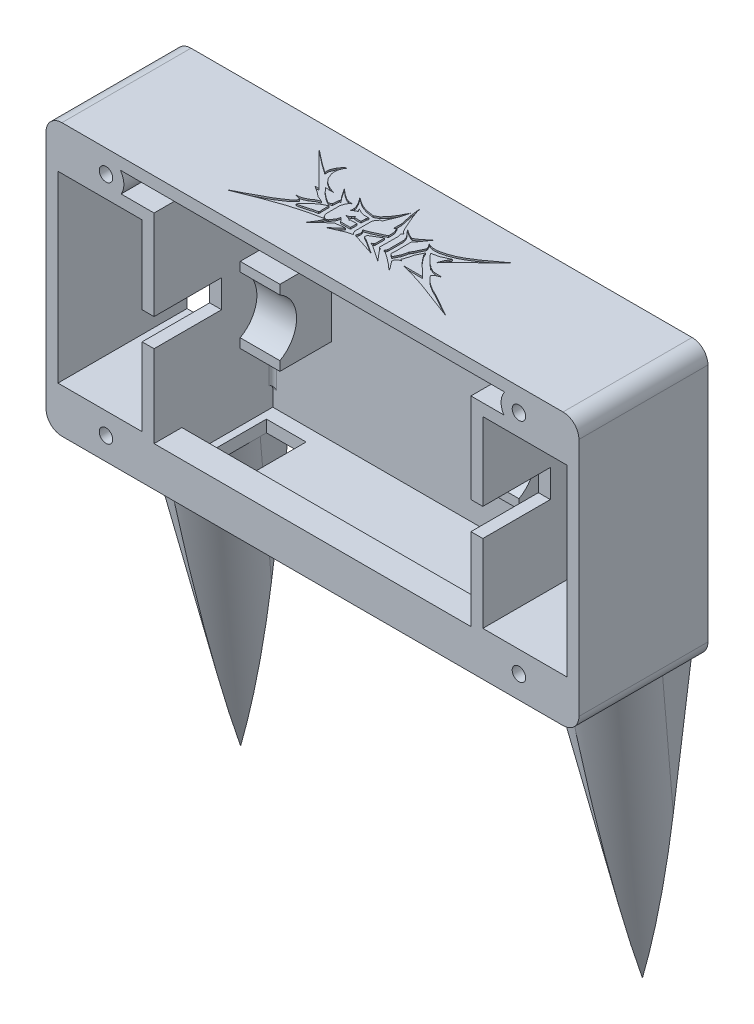
SolidWorks part; units mm, degrees
material "Overture Super PLA Plus"
ref_plane "Front Plane" through (0, 0, 0) normal (0, 0, 1) x (1, 0, 0)
ref_plane "Top Plane" through (0, 0, 0) normal (0, 1, 0) x (1, 0, 0)
ref_plane "Right Plane" through (0, 0, 0) normal (1, 0, 0) x (0, 0, -1)
sketch "Base_Footprint" plane through (0, 0, 0) normal (0, 0, 1) x (1, 0, 0)
  line L1 (-67.1, -34.2) -> (67.1, -34.2)
  line L2 (-67.1, -34.2) -> (-67.1, 34.2)
  line L3 (-67.1, 34.2) -> (67.1, 34.2)
  line L4 (67.1, -34.2) -> (67.1, 34.2)
  dimension "R1_Width" = 134.2
  dimension "R1_Length" = 68.4
  dimension "R1_X" = 67.1
  dimension "R1_Y" = 34.2
extrude "Unbroken_Floor" add sketch "Base_Footprint" along normal blind 2.6
sketch "Shell_Profile" plane through (0, 0, 0) normal (0, 0, 1) x (1, 0, 0)
  line L1 (-67.1, -34.2) -> (67.1, -34.2)
  line L2 (-67.1, -34.2) -> (-67.1, 34.2)
  line L3 (-67.1, 34.2) -> (67.1, 34.2)
  line L4 (67.1, -34.2) -> (67.1, 34.2)
  line L6 (-64.1, -31.2) -> (64.1, -31.2)
  line L7 (-64.1, -31.2) -> (-64.1, 31.2)
  line L8 (-64.1, 31.2) -> (64.1, 31.2)
  line L9 (64.1, -31.2) -> (64.1, 31.2)
  dimension "R1_Width" = 134.2
  dimension "R1_Length" = 68.4
  dimension "R1_X" = 67.1
  dimension "R1_Y" = 34.2
  dimension "R2_Width" = 128.2
  dimension "R2_Length" = 62.4
  dimension "R2_X" = 64.1
  dimension "R2_Y" = 31.2
extrude "Three_mm_Perimeter" add sketch "Shell_Profile" along normal blind 32.5
sketch "Wheel_Well_Profile" plane through (0, 0, 0) normal (0, 0, 1) x (1, 0, 0)
  line L1 (42.9, -23.1) -> (64.1, -23.1)
  line L2 (42.9, -23.1) -> (42.9, 23.1)
  line L3 (42.9, 23.1) -> (64.1, 23.1)
  line L4 (64.1, -23.1) -> (64.1, 23.1)
  line L6 (-64.1, -23.1) -> (-42.9, -23.1)
  line L7 (-64.1, -23.1) -> (-64.1, 23.1)
  line L8 (-64.1, 23.1) -> (-42.9, 23.1)
  line L9 (-42.9, -23.1) -> (-42.9, 23.1)
  dimension "R2_X" = 64.1
  dimension "R1_Width" = 21.2
  dimension "R1_Length" = 46.2
  dimension "R1_X" = 42.9
  dimension "R1_Y" = 23.1
  dimension "R2_Width" = 21.2
  dimension "R2_Length" = 46.2
  dimension "R2_Y" = 23.1
extrude "Open_Wheel_Wells" cut sketch "Wheel_Well_Profile" against normal blind 38 from offset 36
sketch "Wheel_Guard_Profile" plane through (0, 0, 0) normal (0, 0, 1) x (1, 0, 0)
  line L1 (39.9, -23.1) -> (42.9, -23.1)
  line L2 (39.9, -23.1) -> (39.9, 23.1)
  line L3 (39.9, 23.1) -> (42.9, 23.1)
  line L4 (42.9, -23.1) -> (42.9, 23.1)
  line L6 (-42.9, -23.1) -> (-39.9, -23.1)
  line L7 (-42.9, -23.1) -> (-42.9, 23.1)
  line L8 (-42.9, 23.1) -> (-39.9, 23.1)
  line L9 (-39.9, -23.1) -> (-39.9, 23.1)
  dimension "R1_Width" = 3
  dimension "R1_Length" = 46.2
  dimension "R1_X" = 39.9
  dimension "R1_Y" = 23.1
  dimension "R2_Width" = 3
  dimension "R2_Length" = 46.2
  dimension "R2_X" = 42.9
  dimension "R2_Y" = 23.1
extrude "Inner_Wheel_Guards" add sketch "Wheel_Guard_Profile" along normal blind 32.5
sketch "Wheel_Return_Profile" plane through (0, 0, 0) normal (0, 0, 1) x (1, 0, 0)
  line L1 (-64.1, -26.1) -> (-39.9, -26.1)
  line L2 (-64.1, -26.1) -> (-64.1, -23.1)
  line L3 (-64.1, -23.1) -> (-39.9, -23.1)
  line L4 (-39.9, -26.1) -> (-39.9, -23.1)
  line L6 (-64.1, 23.1) -> (-39.9, 23.1)
  line L7 (-64.1, 23.1) -> (-64.1, 26.1)
  line L8 (-64.1, 26.1) -> (-39.9, 26.1)
  line L9 (-39.9, 23.1) -> (-39.9, 26.1)
  line L11 (39.9, -26.1) -> (64.1, -26.1)
  line L12 (39.9, -26.1) -> (39.9, -23.1)
  line L13 (39.9, -23.1) -> (64.1, -23.1)
  line L14 (64.1, -26.1) -> (64.1, -23.1)
  line L16 (39.9, 23.1) -> (64.1, 23.1)
  line L17 (39.9, 23.1) -> (39.9, 26.1)
  line L18 (39.9, 26.1) -> (64.1, 26.1)
  line L19 (64.1, 23.1) -> (64.1, 26.1)
  dimension "R1_Width" = 24.2
  dimension "R1_Length" = 3
  dimension "R1_X" = 64.1
  dimension "R1_Y" = 26.1
  dimension "R2_Width" = 24.2
  dimension "R2_Length" = 3
  dimension "R2_X" = 64.1
  dimension "R2_Y" = 23.1
  dimension "R3_Width" = 24.2
  dimension "R3_Length" = 3
  dimension "R3_X" = 39.9
  dimension "R3_Y" = 26.1
  dimension "R4_Width" = 24.2
  dimension "R4_Length" = 3
  dimension "R4_X" = 39.9
  dimension "R4_Y" = 23.1
extrude "Wheel_Return_Ribs" add sketch "Wheel_Return_Profile" along normal blind 32.5
sketch "Shaft_Drop_In_Profile" plane through (0, 0, 0) normal (0, 0, 1) x (1, 0, 0)
  line L1 (-43.2, -3.5) -> (-39.5, -3.5)
  line L2 (-43.2, -3.5) -> (-43.2, 3.5)
  line L3 (-43.2, 3.5) -> (-39.5, 3.5)
  line L4 (-39.5, -3.5) -> (-39.5, 3.5)
  line L6 (39.5, -3.5) -> (43.2, -3.5)
  line L7 (39.5, -3.5) -> (39.5, 3.5)
  line L8 (39.5, 3.5) -> (43.2, 3.5)
  line L9 (43.2, -3.5) -> (43.2, 3.5)
  dimension "R1_Width" = 3.7
  dimension "R1_Length" = 7
  dimension "R1_X" = 43.2
  dimension "R1_Y" = 3.5
  dimension "R2_Width" = 3.7
  dimension "R2_Length" = 7
  dimension "R2_X" = 39.5
  dimension "R2_Y" = 3.5
extrude "Open_Shaft_Notches" cut sketch "Shaft_Drop_In_Profile" against normal blind 17 from offset 32.5
sketch "Lower_Cradle_Blocks_Profile" plane through (0, 0, 0) normal (0, 0, 1) x (1, 0, 0)
  line L1 (-35.1, -9.5) -> (-25.1, -9.5)
  line L2 (-35.1, -9.5) -> (-35.1, 9.5)
  line L3 (-35.1, 9.5) -> (-25.1, 9.5)
  line L4 (-25.1, -9.5) -> (-25.1, 9.5)
  line L6 (25.1, -9.5) -> (35.1, -9.5)
  line L7 (25.1, -9.5) -> (25.1, 9.5)
  line L8 (25.1, 9.5) -> (35.1, 9.5)
  line L9 (35.1, -9.5) -> (35.1, 9.5)
  dimension "R1_Width" = 10
  dimension "R1_Length" = 19
  dimension "R1_X" = 35.1
  dimension "R1_Y" = 9.5
  dimension "R2_Width" = 10
  dimension "R2_Length" = 19
  dimension "R2_X" = 25.1
  dimension "R2_Y" = 9.5
extrude "Lower_Motor_Cradles" add sketch "Lower_Cradle_Blocks_Profile" along normal blind 15.6
sketch "Lower_Cradle_Radius_Profile" plane through (0, 0, 0) normal (1, 0, 0) x (0, 0, -1)
  circle A0 centre (-19.6, 0) radius 8.2
  dimension "C1_Diameter" = 16.4
  dimension "Motor_Axis_Height" = 19.6
extrude "Lower_Cradle_Seats_R8p2" cut sketch "Lower_Cradle_Radius_Profile" against normal blind 72 from offset 36
sketch "Battery_Side_Guides_Profile" plane through (0, 0, 0) normal (0, 0, 1) x (1, 0, 0)
  line L1 (-31.5, 10) -> (-28.5, 10)
  line L2 (-31.5, 10) -> (-31.5, 31.2)
  line L3 (-31.5, 31.2) -> (-28.5, 31.2)
  line L4 (-28.5, 10) -> (-28.5, 31.2)
  line L6 (28.5, 10) -> (31.5, 10)
  line L7 (28.5, 10) -> (28.5, 31.2)
  line L8 (28.5, 31.2) -> (31.5, 31.2)
  line L9 (31.5, 10) -> (31.5, 31.2)
  dimension "R1_Width" = 3
  dimension "R1_Length" = 21.2
  dimension "R1_X" = 31.5
  dimension "R1_Y" = 10
  dimension "R2_Width" = 3
  dimension "R2_Length" = 21.2
  dimension "R2_X" = 28.5
  dimension "R2_Y" = 10
extrude "Battery_Side_Guides" add sketch "Battery_Side_Guides_Profile" along normal blind 5.6
sketch "Lid_Screw_Boss_Profile" plane through (0, 0, 0) normal (0, 0, 1) x (1, 0, 0)
  circle A0 centre (-52, -28.5) radius 4.5
  circle A1 centre (-52, 28.5) radius 4.5
  circle A2 centre (52, -28.5) radius 4.5
  circle A3 centre (52, 28.5) radius 4.5
  dimension "C1_Diameter" = 9
  dimension "C2_Diameter" = 9
  dimension "C3_Diameter" = 9
  dimension "C4_Diameter" = 9
extrude "Reinforced_M3_Bosses" add sketch "Lid_Screw_Boss_Profile" along normal blind 32.5
sketch "M3_Through_Holes_Profile" plane through (0, 0, 0) normal (0, 0, 1) x (1, 0, 0)
  circle A0 centre (-52, -28.5) radius 1.7
  circle A1 centre (-52, 28.5) radius 1.7
  circle A2 centre (52, -28.5) radius 1.7
  circle A3 centre (52, 28.5) radius 1.7
  dimension "C1_Diameter" = 3.4
  dimension "C2_Diameter" = 3.4
  dimension "C3_Diameter" = 3.4
  dimension "C4_Diameter" = 3.4
extrude "M3_Through_Holes" cut sketch "M3_Through_Holes_Profile" against normal blind 36 from offset 35.5
sketch "Captive_Nut_Pockets_Profile" plane through (0, 0, 0) normal (0, 0, 1) x (1, 0, 0)
  line L0 (-48.7091, -28.5) -> (-50.3546, -25.65)
  line L1 (-50.3546, -25.65) -> (-53.6454, -25.65)
  line L2 (-53.6454, -25.65) -> (-55.2909, -28.5)
  line L3 (-55.2909, -28.5) -> (-53.6454, -31.35)
  line L4 (-53.6454, -31.35) -> (-50.3546, -31.35)
  line L5 (-50.3546, -31.35) -> (-48.7091, -28.5)
  line L6 (-48.7091, 28.5) -> (-50.3546, 31.35)
  line L7 (-50.3546, 31.35) -> (-53.6454, 31.35)
  line L8 (-53.6454, 31.35) -> (-55.2909, 28.5)
  line L9 (-55.2909, 28.5) -> (-53.6454, 25.65)
  line L10 (-53.6454, 25.65) -> (-50.3546, 25.65)
  line L11 (-50.3546, 25.65) -> (-48.7091, 28.5)
  line L12 (55.2909, -28.5) -> (53.6454, -25.65)
  line L13 (53.6454, -25.65) -> (50.3546, -25.65)
  line L14 (50.3546, -25.65) -> (48.7091, -28.5)
  line L15 (48.7091, -28.5) -> (50.3546, -31.35)
  line L16 (50.3546, -31.35) -> (53.6454, -31.35)
  line L17 (53.6454, -31.35) -> (55.2909, -28.5)
  line L18 (55.2909, 28.5) -> (53.6454, 31.35)
  line L19 (53.6454, 31.35) -> (50.3546, 31.35)
  line L20 (50.3546, 31.35) -> (48.7091, 28.5)
  line L21 (48.7091, 28.5) -> (50.3546, 25.65)
  line L22 (50.3546, 25.65) -> (53.6454, 25.65)
  line L23 (53.6454, 25.65) -> (55.2909, 28.5)
extrude "M3_Hex_Nut_Pockets_Underside" cut sketch "Captive_Nut_Pockets_Profile" against normal blind 2.7 from offset 2.6
fillet "Outer_Corners_R4" radius 4 4 edges at (-67.1, 34.2, 16.25) (67.1, 34.2, 16.25) (67.1, -34.2, 16.25) (-67.1, -34.2, 16.25) tangent propagation no
fillet "Inner_Corners_R1" radius 1 4 edges at (-64.1, 31.2, 17.55) (64.1, 31.2, 17.55) (64.1, -31.2, 17.55) (-64.1, -31.2, 17.55) tangent propagation no
fillet "Wheel_Return_Root_Fillets_R1" radius 1 10 edges at (-44.0467, -26.1, 2.6) (-59.9533, -26.1, 2.6) (44.0467, 26.1, 2.6) (59.9533, 26.1, 2.6) (59.9533, -26.1, 2.6) (44.0467, -26.1, 2.6) (-59.9533, 26.1, 2.6) (-44.0467, 26.1, 2.6) (-39.9, 0, 2.6) (39.9, 0, 2.6) tangent propagation no
sketch "VIPER_Wordmark_Native_Profile" plane through (0, 0, 0) normal (0, 1, 0) x (1, 0, 0)
  line L0 (27.5, -26.3235) -> (17.4068, -22.5385)
  line L1 (17.4068, -22.5385) -> (13.8978, -21.4346)
  line L2 (13.8978, -21.4346) -> (11.3351, -20.7643)
  line L3 (11.3351, -20.7643) -> (11.2957, -20.6855)
  line L4 (11.2957, -20.6855) -> (15.948, -20.6855)
  line L5 (15.948, -20.6855) -> (14.2133, -18.9507)
  line L6 (14.2133, -18.9507) -> (13.543, -18.4776)
  line L7 (13.543, -18.4776) -> (12.3208, -17.1371)
  line L8 (12.3208, -17.1371) -> (11.3746, -15.8754)
  line L9 (11.3746, -15.8754) -> (11.0986, -15.1658)
  line L10 (11.0986, -15.1658) -> (10.0735, -17.2159)
  line L11 (10.0735, -17.2159) -> (10.0735, -17.6496)
  line L12 (10.0735, -17.6496) -> (9.5609, -19.2267)
  line L13 (9.5609, -19.2267) -> (9.3638, -19.5815)
  line L14 (9.3638, -19.5815) -> (9.7975, -19.8181)
  line L15 (9.7975, -19.8181) -> (9.7975, -19.897)
  line L16 (9.7975, -19.897) -> (9.5215, -19.9364)
  line L17 (9.5215, -19.9364) -> (9.0878, -20.2124)
  line L18 (9.0878, -20.2124) -> (8.7724, -20.5278)
  line L19 (8.7724, -20.5278) -> (8.6147, -20.8432)
  line L20 (8.6147, -20.8432) -> (8.6541, -21.2375)
  line L21 (8.6541, -21.2375) -> (9.7581, -22.6568)
  line L22 (9.7581, -22.6568) -> (10.31, -23.4453)
  line L23 (10.31, -23.4453) -> (10.2706, -23.5242)
  line L24 (10.2706, -23.5242) -> (9.1272, -22.4597)
  line L25 (9.1272, -22.4597) -> (7.1559, -20.922)
  line L26 (7.1559, -20.922) -> (5.9731, -20.1335)
  line L27 (5.9731, -20.1335) -> (5.224, -19.8575)
  line L28 (5.224, -19.8575) -> (5.4211, -19.621)
  line L29 (5.4211, -19.621) -> (5.6183, -19.069)
  line L30 (5.6183, -19.069) -> (5.6183, -15.2446)
  line L31 (5.6183, -15.2446) -> (5.5394, -14.8504)
  line L32 (5.5394, -14.8504) -> (5.224, -14.0224)
  line L33 (5.224, -14.0224) -> (3.6864, -12.2482)
  line L34 (3.6864, -12.2482) -> (5.0269, -13.155)
  line L35 (5.0269, -13.155) -> (5.9731, -13.6281)
  line L36 (5.9731, -13.6281) -> (6.2491, -13.6676)
  line L37 (6.2491, -13.6676) -> (7.4713, -12.879)
  line L38 (7.4713, -12.879) -> (9.3244, -11.3414)
  line L39 (9.3244, -11.3414) -> (7.6685, -13.707)
  line L40 (7.6685, -13.707) -> (6.9194, -14.5744)
  line L41 (6.9194, -14.5744) -> (6.9588, -18.1228)
  line L42 (6.9588, -18.1228) -> (6.8799, -19.5815)
  line L43 (6.8799, -19.5815) -> (7.629, -20.2518)
  line L44 (7.629, -20.2518) -> (8.457, -18.5959)
  line L45 (8.457, -18.5959) -> (8.8513, -17.0188)
  line L46 (8.8513, -17.0188) -> (9.2849, -16.3091)
  line L47 (9.2849, -16.3091) -> (10.3495, -14.0224)
  line L48 (10.3495, -14.0224) -> (10.1918, -13.5887)
  line L49 (10.1918, -13.5887) -> (9.6398, -12.7213)
  line L50 (9.6398, -12.7213) -> (10.2312, -12.9973)
  line L51 (10.2312, -12.9973) -> (10.9014, -13.155)
  line L52 (10.9014, -13.155) -> (12.1237, -13.155)
  line L53 (12.1237, -13.155) -> (13.9767, -12.7213)
  line L54 (13.9767, -12.7213) -> (15.7115, -12.0511)
  line L55 (15.7115, -12.0511) -> (17.3674, -11.1837)
  line L56 (17.3674, -11.1837) -> (19.5358, -9.8038)
  line L57 (19.5358, -9.8038) -> (24.267, -6.3342)
  line L58 (24.267, -6.3342) -> (20.0484, -10.474)
  line L59 (20.0484, -10.474) -> (17.4068, -12.9185)
  line L60 (17.4068, -12.9185) -> (15.5932, -14.7321)
  line L61 (15.5932, -14.7321) -> (14.6864, -15.836)
  line L62 (14.6864, -15.836) -> (14.647, -15.7177)
  line L63 (14.647, -15.7177) -> (15.0806, -14.6138)
  line L64 (15.0806, -14.6138) -> (15.8692, -13.155)
  line L65 (15.8692, -13.155) -> (13.6219, -14.1801)
  line L66 (13.6219, -14.1801) -> (11.7688, -14.5744)
  line L67 (11.7688, -14.5744) -> (13.5036, -16.4668)
  line L68 (13.5036, -16.4668) -> (14.4104, -17.2159)
  line L69 (14.4104, -17.2159) -> (14.7258, -17.3737)
  line L70 (14.7258, -17.3737) -> (15.0018, -17.7679)
  line L71 (15.0018, -17.7679) -> (15.1201, -17.6891)
  line L72 (15.1201, -17.6891) -> (15.9086, -18.1228)
  line L73 (15.9086, -18.1228) -> (16.5, -18.2805)
  line L74 (16.5, -18.2805) -> (18.4713, -18.3593)
  line L75 (18.4713, -18.3593) -> (17.2097, -18.8719)
  line L76 (17.2097, -18.8719) -> (16.8154, -19.1478)
  line L77 (16.8154, -19.1478) -> (16.6577, -19.3844)
  line L78 (16.6577, -19.3844) -> (17.1308, -20.0941)
  line L79 (17.1308, -20.0941) -> (18.5502, -21.3557)
  line L80 (18.5502, -21.3557) -> (20.0878, -22.302)
  line L81 (20.0878, -22.302) -> (21.31, -22.8934)
  line L82 (21.31, -22.8934) -> (27.5, -26.3235)
  line L83 (-27.4211, -26.2841) -> (-27.5, -26.2841)
  line L84 (-27.5, -26.2841) -> (-27.4606, -26.2052)
  line L85 (-27.4606, -26.2052) -> (-25.0161, -24.983)
  line L86 (-25.0161, -24.983) -> (-19.9695, -22.2231)
  line L87 (-19.9695, -22.2231) -> (-17.6039, -20.6461)
  line L88 (-17.6039, -20.6461) -> (-16.6971, -19.7787)
  line L89 (-16.6971, -19.7787) -> (-16.4211, -19.345)
  line L90 (-16.4211, -19.345) -> (-16.8943, -19.1084)
  line L91 (-16.8943, -19.1084) -> (-18.0771, -18.793)
  line L92 (-18.0771, -18.793) -> (-17.1308, -18.7536)
  line L93 (-17.1308, -18.7536) -> (-16.3029, -18.5565)
  line L94 (-16.3029, -18.5565) -> (-15.3961, -18.1228)
  line L95 (-15.3961, -18.1228) -> (-14.2527, -17.3342)
  line L96 (-14.2527, -17.3342) -> (-13.3065, -16.9794)
  line L97 (-13.3065, -16.9794) -> (-14.3315, -16.5063)
  line L98 (-14.3315, -16.5063) -> (-14.6075, -16.4668)
  line L99 (-14.6075, -16.4668) -> (-15.7903, -15.5206)
  line L100 (-15.7903, -15.5206) -> (-17.4068, -14.4955)
  line L101 (-17.4068, -14.4955) -> (-16.4211, -14.4955)
  line L102 (-16.4211, -14.4955) -> (-24.6219, -6.2554)
  line L103 (-24.6219, -6.2554) -> (-24.6219, -6.1765)
  line L104 (-24.6219, -6.1765) -> (-24.4642, -6.2554)
  line L105 (-24.4642, -6.2554) -> (-21.5466, -8.5421)
  line L106 (-21.5466, -8.5421) -> (-19.1416, -10.2375)
  line L107 (-19.1416, -10.2375) -> (-19.181, -9.4095)
  line L108 (-19.181, -9.4095) -> (-19.1022, -8.9758)
  line L109 (-19.1022, -8.9758) -> (-18.629, -7.8719)
  line L110 (-18.629, -7.8719) -> (-18.1165, -7.1622)
  line L111 (-18.1165, -7.1622) -> (-17.0914, -6.1765)
  line L112 (-17.0914, -6.1765) -> (-17.7616, -7.3593)
  line L113 (-17.7616, -7.3593) -> (-18.0376, -8.1873)
  line L114 (-18.0376, -8.1873) -> (-18.0771, -9.2518)
  line L115 (-18.0771, -9.2518) -> (-17.9588, -9.8038)
  line L116 (-17.9588, -9.8038) -> (-17.3674, -11.2231)
  line L117 (-17.3674, -11.2231) -> (-16.6183, -12.0511)
  line L118 (-16.6183, -12.0511) -> (-15.7115, -12.6819)
  line L119 (-15.7115, -12.6819) -> (-14.8441, -13.1156)
  line L120 (-14.8441, -13.1156) -> (-13.7007, -13.5099)
  line L121 (-13.7007, -13.5099) -> (-14.9229, -13.5493)
  line L122 (-14.9229, -13.5493) -> (-15.8297, -13.3916)
  line L123 (-15.8297, -13.3916) -> (-14.6864, -14.6138)
  line L124 (-14.6864, -14.6138) -> (-13.3065, -15.7177)
  line L125 (-13.3065, -15.7177) -> (-12.0842, -16.4668)
  line L126 (-12.0842, -16.4668) -> (-11.3351, -16.112)
  line L127 (-11.3351, -16.112) -> (-11.2563, -14.6138)
  line L128 (-11.2563, -14.6138) -> (-11.2168, -14.4561)
  line L129 (-11.2168, -14.4561) -> (-10.9409, -14.4167)
  line L130 (-10.9409, -14.4167) -> (-11.8082, -13.3127)
  line L131 (-11.8082, -13.3127) -> (-13.1093, -11.3808)
  line L132 (-13.1093, -11.3808) -> (-11.7688, -12.4848)
  line L133 (-11.7688, -12.4848) -> (-10.6649, -13.2339)
  line L134 (-10.6649, -13.2339) -> (-9.7975, -13.5887)
  line L135 (-9.7975, -13.5887) -> (-8.8513, -13.6281)
  line L136 (-8.8513, -13.6281) -> (-9.3638, -14.1013)
  line L137 (-9.3638, -14.1013) -> (-9.6398, -14.4955)
  line L138 (-9.6398, -14.4955) -> (-9.9946, -15.5206)
  line L139 (-9.9946, -15.5206) -> (-9.9946, -19.1478)
  line L140 (-9.9946, -19.1478) -> (-9.6398, -19.897)
  line L141 (-9.6398, -19.897) -> (-9.0484, -20.3306)
  line L142 (-9.0484, -20.3306) -> (-12.8728, -21.1586)
  line L143 (-12.8728, -21.1586) -> (-16.8548, -22.302)
  line L144 (-16.8548, -22.302) -> (-21.2312, -23.8396)
  line L145 (-21.2312, -23.8396) -> (-27.4211, -26.2841)
  line L146 (-10.586, -23.5636) -> (-10.6254, -23.4848)
  line L147 (-10.6254, -23.4848) -> (-9.4427, -21.6317)
  line L148 (-9.4427, -21.6317) -> (-8.8513, -20.2912)
  line L149 (-8.8513, -20.2912) -> (-8.5753, -20.2912)
  line L150 (-8.5753, -20.2912) -> (-8.3781, -20.1335)
  line L151 (-8.3781, -20.1335) -> (-7.5502, -18.9113)
  line L152 (-7.5502, -18.9113) -> (-7.2742, -18.0045)
  line L153 (-7.2742, -18.0045) -> (-6.3674, -19.0296)
  line L154 (-6.3674, -19.0296) -> (-3.9229, -19.0296)
  line L155 (-3.9229, -19.0296) -> (-3.9229, -17.3737)
  line L156 (-3.9229, -17.3737) -> (-5.5789, -17.4131)
  line L157 (-5.5789, -17.4131) -> (-5.6183, -17.7679)
  line L158 (-5.6183, -17.7679) -> (-5.776, -17.5314)
  line L159 (-5.776, -17.5314) -> (-6.1308, -17.2948)
  line L160 (-6.1308, -17.2948) -> (-7.1559, -16.9794)
  line L161 (-7.1559, -16.9794) -> (-6.6039, -16.8217)
  line L162 (-6.6039, -16.8217) -> (-6.1308, -16.5457)
  line L163 (-6.1308, -16.5457) -> (-5.6183, -15.9937)
  line L164 (-5.6183, -15.9937) -> (-5.5394, -16.388)
  line L165 (-5.5394, -16.388) -> (-3.9229, -16.3486)
  line L166 (-3.9229, -16.3486) -> (-3.8835, -15.0869)
  line L167 (-3.8835, -15.0869) -> (-3.6864, -14.6138)
  line L168 (-3.6864, -14.6138) -> (-4.6326, -14.6532)
  line L169 (-4.6326, -14.6532) -> (-5.5, -14.5349)
  line L170 (-5.5, -14.5349) -> (-6.8011, -13.9041)
  line L171 (-6.8011, -13.9041) -> (-6.6039, -14.3772)
  line L172 (-6.6039, -14.3772) -> (-6.3674, -14.4561)
  line L173 (-6.3674, -14.4561) -> (-6.3674, -14.5349)
  line L174 (-6.3674, -14.5349) -> (-6.9588, -14.8109)
  line L175 (-6.9588, -14.8109) -> (-7.7079, -15.4023)
  line L176 (-7.7079, -15.4023) -> (-7.5896, -14.9686)
  line L177 (-7.5896, -14.9686) -> (-7.5896, -14.2984)
  line L178 (-7.5896, -14.2984) -> (-7.7867, -13.6281)
  line L179 (-7.7867, -13.6281) -> (-8.3387, -12.5636)
  line L180 (-8.3387, -12.5636) -> (-9.2455, -11.302)
  line L181 (-9.2455, -11.302) -> (-7.7079, -12.4059)
  line L182 (-7.7079, -12.4059) -> (-6.6828, -12.9185)
  line L183 (-6.6828, -12.9185) -> (-5.4606, -13.3127)
  line L184 (-5.4606, -13.3127) -> (-3.6075, -13.5887)
  line L185 (-3.6075, -13.5887) -> (-2.543, -12.9973)
  line L186 (-2.543, -12.9973) -> (-1.5573, -11.9722)
  line L187 (-1.5573, -11.9722) -> (-0.414, -10.2375)
  line L188 (-0.414, -10.2375) -> (0.6505, -8.069)
  line L189 (0.6505, -8.069) -> (-0.0986, -10.7106)
  line L190 (-0.0986, -10.7106) -> (-1.3602, -13.707)
  line L191 (-1.3602, -13.707) -> (-1.5179, -13.5887)
  line L192 (-1.5179, -13.5887) -> (-1.7545, -13.707)
  line L193 (-1.7545, -13.707) -> (-2.1093, -14.1013)
  line L194 (-2.1093, -14.1013) -> (-2.5824, -14.8898)
  line L195 (-2.5824, -14.8898) -> (-2.5824, -19.2267)
  line L196 (-2.5824, -19.2267) -> (-2.3459, -19.7787)
  line L197 (-2.3459, -19.7787) -> (-1.9516, -20.1729)
  line L198 (-1.9516, -20.1729) -> (-3.4104, -20.5672)
  line L199 (-3.4104, -20.5672) -> (-7.1953, -22.2231)
  line L200 (-7.1953, -22.2231) -> (-5.9731, -21.2769)
  line L201 (-5.9731, -21.2769) -> (-4.3961, -19.8575)
  line L202 (-4.3961, -19.8575) -> (-4.3961, -19.7787)
  line L203 (-4.3961, -19.7787) -> (-5.1452, -19.8181)
  line L204 (-5.1452, -19.8181) -> (-6.8799, -20.0941)
  line L205 (-6.8799, -20.0941) -> (-8.733, -21.6711)
  line L206 (-8.733, -21.6711) -> (-10.586, -23.5636)
  line L207 (6.8405, -22.8934) -> (3.2527, -20.4884)
  line L208 (3.2527, -20.4884) -> (3.1344, -20.3306)
  line L209 (3.1344, -20.3306) -> (2.0699, -19.8575)
  line L210 (2.0699, -19.8575) -> (2.5036, -19.6604)
  line L211 (2.5036, -19.6604) -> (2.7007, -19.4238)
  line L212 (2.7007, -19.4238) -> (2.7007, -17.0188)
  line L213 (2.7007, -17.0188) -> (-0.0591, -18.6747)
  line L214 (-0.0591, -18.6747) -> (-0.0986, -19.3056)
  line L215 (-0.0986, -19.3056) -> (0.8871, -19.8181)
  line L216 (0.8871, -19.8181) -> (4.3566, -22.0654)
  line L217 (4.3566, -22.0654) -> (-1.3996, -20.1729)
  line L218 (-1.3996, -20.1729) -> (-1.6362, -20.0152)
  line L219 (-1.6362, -20.0152) -> (-1.3996, -19.345)
  line L220 (-1.3996, -19.345) -> (-1.3996, -18.793)
  line L221 (-1.3996, -18.793) -> (-1.5573, -18.3593)
  line L222 (-1.5573, -18.3593) -> (-1.7939, -18.0833)
  line L223 (-1.7939, -18.0833) -> (-1.7545, -18.0045)
  line L224 (-1.7545, -18.0045) -> (-0.2957, -17.4525)
  line L225 (-0.2957, -17.4525) -> (2.7007, -16.0332)
  line L226 (2.7007, -16.0332) -> (2.6613, -14.6532)
  line L227 (2.6613, -14.6532) -> (2.5036, -14.0618)
  line L228 (2.5036, -14.0618) -> (2.2276, -13.707)
  line L229 (2.2276, -13.707) -> (2.1882, -13.431)
  line L230 (2.1882, -13.431) -> (1.6756, -13.7464)
  line L231 (1.6756, -13.7464) -> (1.7545, -11.8539)
  line L232 (1.7545, -11.8539) -> (1.1237, -8.897)
  line L233 (1.1237, -8.897) -> (0.8082, -6.4131)
  line L234 (0.8082, -6.4131) -> (0.8871, -6.4525)
  line L235 (0.8871, -6.4525) -> (1.0448, -7.1622)
  line L236 (1.0448, -7.1622) -> (1.7151, -9.0152)
  line L237 (1.7151, -9.0152) -> (3.0556, -12.1299)
  line L238 (3.0556, -12.1299) -> (3.6864, -13.3127)
  line L239 (3.6864, -13.3127) -> (4.0806, -13.6281)
  line L240 (4.0806, -13.6281) -> (4.2778, -13.6676)
  line L241 (4.2778, -13.6676) -> (3.8835, -14.1013)
  line L242 (3.8835, -14.1013) -> (4.0806, -15.0081)
  line L243 (4.0806, -15.0081) -> (4.0412, -19.621)
  line L244 (4.0412, -19.621) -> (4.2384, -19.8181)
  line L245 (4.2384, -19.8181) -> (4.4749, -19.897)
  line L246 (4.4749, -19.897) -> (5.0269, -20.7249)
  line L247 (5.0269, -20.7249) -> (6.8405, -22.8934)
  line L248 (-15.9086, -20.6855) -> (-15.7903, -20.7249)
  line L249 (-15.7903, -20.7249) -> (-14.5681, -20.4489)
  line L250 (-14.5681, -20.4489) -> (-12.3996, -19.8181)
  line L251 (-12.3996, -19.8181) -> (-11.3746, -19.621)
  line L252 (-11.3746, -19.621) -> (-11.2563, -19.3056)
  line L253 (-11.2563, -19.3056) -> (-11.3351, -18.9113)
  line L254 (-11.3351, -18.9113) -> (-11.3351, -17.0188)
  line L255 (-11.3351, -17.0188) -> (-12.6362, -17.6496)
  line L256 (-12.6362, -17.6496) -> (-13.819, -18.517)
  line L257 (-13.819, -18.517) -> (-15.9086, -20.6855)
extrude "VIPER_Rear_Engraved" cut sketch "VIPER_Wordmark_Native_Profile" against normal blind 0.4 from offset 34.2
sketch "Sketch1" plane through (0, 0, 0) normal (0, 0, 1) x (1, 0, 0)
  line L0 (0, 0) -> (0, -36.802) construction
  line L1 (-48.4, -31.2) -> (-39.9, -31.2)
  line L2 (-48.4, -31.2) -> (-48.4, -26.1)
  line L3 (-48.4, -26.1) -> (-39.9, -26.1)
  line L4 (-39.9, -31.2) -> (-39.9, -26.1)
  line L5 (48.4, -31.2) -> (48.4, -26.1)
  line L6 (48.4, -26.1) -> (39.9, -26.1)
  line L7 (39.9, -31.2) -> (39.9, -26.1)
  line L8 (48.4, -31.2) -> (39.9, -31.2)
extrude "Boss-Extrude1" add sketch "Sketch1" along normal blind 32.5
sketch "Sketch2" plane through (-39.9, 0, 0) normal (1, 0, 0) x (0, 0, -1)
  line L1 (-32.5, -31.2) -> (-25.5, -31.2)
  line L2 (-32.5, -31.2) -> (-32.5, -24.2)
  line L3 (-32.5, -24.2) -> (-25.5, -24.2)
  line L4 (-25.5, -31.2) -> (-25.5, -24.2)
  dimension "D1" = 7
  dimension "D2" = 7
extrude "Boss-Extrude2" add sketch "Sketch2" along normal blind 82.5 and the other way blind 2
sketch "Sketch3" plane through (0, 0, 0) normal (0, 0, 1) x (1, 0, 0)
  line L1 (-55.6, 31.2) -> (-64.1, 31.2)
  line L2 (-55.6, 31.2) -> (-55.6, 26.1)
  line L3 (-55.6, 26.1) -> (-64.1, 26.1)
  line L4 (-64.1, 31.2) -> (-64.1, 26.1)
  line L5 (-55.6, -31.2) -> (-64.1, -31.2)
  line L6 (-55.6, -31.2) -> (-55.6, -26.1)
  line L7 (-55.6, -26.1) -> (-64.1, -26.1)
  line L8 (-64.1, -31.2) -> (-64.1, -26.1)
  line L9 (55.6, -31.2) -> (64.1, -31.2)
  line L10 (55.6, -31.2) -> (55.6, -26.1)
  line L11 (55.6, -26.1) -> (64.1, -26.1)
  line L12 (64.1, -31.2) -> (64.1, -26.1)
  line L13 (55.6, 31.2) -> (64.1, 31.2)
  line L14 (55.6, 31.2) -> (55.6, 26.1)
  line L15 (55.6, 26.1) -> (64.1, 26.1)
  line L16 (64.1, 31.2) -> (64.1, 26.1)
extrude "Boss-Extrude5" add sketch "Sketch3" along normal blind 32.5
sketch "Forks" plane through (0, -34.2, 0) normal (0, -1, 0) x (1, 0, 0)
  line L0 (0, 0) -> (0, 32.5) construction
  line L1 (-63.1, 32.5) -> (63.1, 32.5) construction
  line L2 (-63.1, 0) -> (63.1, 0) construction
  line L3 (-63.1, 32.5) -> (-38.1, 32.5)
  line L4 (-63.1, 32.5) -> (-63.1, 0)
  line L5 (-63.1, 0) -> (-38.1, 0)
  line L6 (-38.1, 32.5) -> (-38.1, 0)
  line L7 (63.1, 0) -> (38.1, 0)
  line L8 (38.1, 32.5) -> (38.1, 0)
  line L9 (63.1, 32.5) -> (38.1, 32.5)
  line L10 (63.1, 32.5) -> (63.1, 0)
  dimension "D1" = 25
sketch "Sketch4" plane through (0, -34.2, 0) normal (0, -1, 0) x (1, 0, 0)
  line L0 (-38.1, 32.5) -> (-38.1, 0) construction
  line L1 (-38.1, 24) -> (-28.1, 24)
  line L2 (-38.1, 24) -> (-38.1, 6)
  line L3 (-38.1, 6) -> (-28.1, 6)
  line L4 (-28.1, 24) -> (-28.1, 6)
  line L5 (-63.1, 0) -> (63.1, 0) construction
  dimension "D1" = 18
  dimension "D2" = 6
  dimension "D3" = 10
extrude "Cut-Extrude1" cut sketch "Sketch4" against normal blind 10
sketch "Sketch6" plane through (0, 0, 0) normal (0, 0, 1) x (1, 0, 0)
  line L0 (-50.6, -34.2) -> (-50.6, -134.2) construction
  line L1 (-63.1, -34.2) -> (-38.1, -34.2) construction
  line L2 (-38.1, -34.2) -> (-63.1, -34.2)
  line L3 (-63.1, -34.2) -> (-50.6, -134.2)
  line L4 (-38.1, -34.2) -> (-50.6, -134.2)
  line L5 (0, -34.2) -> (0, -134.2) construction
  line L6 (-63.1, -34.2) -> (63.1, -34.2) construction
  line L7 (38.1, -34.2) -> (63.1, -34.2)
  line L8 (38.1, -34.2) -> (50.6, -134.2)
  line L9 (63.1, -34.2) -> (50.6, -134.2)
  dimension "D1" = 100
  dimension "D2" = 12.5
extrude "Boss-Extrude7" add sketch "Sketch6" along normal blind 20
sketch "Sketch8" plane through (0, 0, 0) normal (1, 0, 0) x (0, 0, -1)
  line L0 (-20, -34.2) -> (0, -134.2)
  line L1 (0, -134.2) -> (-20, -134.2)
  line L2 (-20, -134.2) -> (-20, -34.2)
extrude "Cut-Extrude3" cut sketch "Sketch8" against normal blind 78 and the other way blind 70
fillet "Fillet3" radius 12.5 4 edges at (-44.35, -84.2, 10) (-56.85, -84.2, 10) (44.35, -84.2, 10) (56.85, -84.2, 10)
equation "\"Overall_Width\"= 134.2mm"
equation "\"Overall_Length\"= 68.4mm"
equation "\"Wall\"= 3mm"
equation "\"Floor\"= 2.6mm"
equation "\"Case_Height\"= 32.5mm"
equation "\"Lid_Thickness\"= 3mm"
equation "\"Wheel_Diameter\"= 43.2mm"
equation "\"Wheel_Width\"= 14mm"
equation "\"Wheel_Bay_Inner_X\"= 42.9mm"
equation "\"Wheel_Radial_Clearance\"= 1.5mm"
equation "\"Wheel_Bay_Half_Length\"= \"Wheel_Diameter\"/2+\"Wheel_Radial_Clearance\""
equation "\"Ground_Clearance\"= 2mm"
equation "\"Motor_Axis_Z\"= \"Wheel_Diameter\"/2-\"Ground_Clearance\""
equation "\"Motor_Face_X\"= 38.1mm"
equation "\"Motor_Clamp_Radius\"= 8.2mm"
equation "\"Screw_Clearance\"= 3.4mm"
equation "\"Nut_AF_Clearance\"= 5.7mm"
equation "\"Engraving_Depth\"= 0.4mm"
equation "\"Hub_Offset_Min_Allowed\"= \"Wheel_Bay_Inner_X\"+1mm-\"Motor_Face_X\""
equation "\"Hub_Offset_Max_Allowed\"= \"Overall_Width\"/2-\"Wall\"-1mm-\"Wheel_Width\"-\"Motor_Face_X\""
equation "\"R1_Width@Base_Footprint\" = \"Overall_Width\""
equation "\"R1_Length@Base_Footprint\" = \"Overall_Length\""
equation "\"R1_X@Base_Footprint\" = \"Overall_Width\"/2"
equation "\"R1_Y@Base_Footprint\" = \"Overall_Length\"/2"
equation "\"D1@Unbroken_Floor\" = \"Floor\""
equation "\"R1_Width@Shell_Profile\" = \"Overall_Width\""
equation "\"R1_Length@Shell_Profile\" = \"Overall_Length\""
equation "\"R1_X@Shell_Profile\" = \"Overall_Width\"/2"
equation "\"R1_Y@Shell_Profile\" = \"Overall_Length\"/2"
equation "\"R2_Width@Shell_Profile\" = \"Overall_Width\"-2*\"Wall\""
equation "\"R2_Length@Shell_Profile\" = \"Overall_Length\"-2*\"Wall\""
equation "\"R2_X@Shell_Profile\" = \"Overall_Width\"/2-\"Wall\""
equation "\"R2_Y@Shell_Profile\" = \"Overall_Length\"/2-\"Wall\""
equation "\"D1@Three_mm_Perimeter\" = \"Case_Height\""
equation "\"R1_Width@Wheel_Well_Profile\" = \"Overall_Width\"/2-\"Wall\"-\"Wheel_Bay_Inner_X\""
equation "\"R1_Length@Wheel_Well_Profile\" = 2*\"Wheel_Bay_Half_Length\""
equation "\"R1_X@Wheel_Well_Profile\" = \"Wheel_Bay_Inner_X\""
equation "\"R1_Y@Wheel_Well_Profile\" = \"Wheel_Bay_Half_Length\""
equation "\"R2_Width@Wheel_Well_Profile\" = \"Overall_Width\"/2-\"Wall\"-\"Wheel_Bay_Inner_X\""
equation "\"R2_Length@Wheel_Well_Profile\" = 2*\"Wheel_Bay_Half_Length\""
equation "\"R2_X@Wheel_Well_Profile\" = \"Overall_Width\"/2-\"Wall\""
equation "\"R2_Y@Wheel_Well_Profile\" = \"Wheel_Bay_Half_Length\""
equation "\"D1@Inner_Wheel_Guards\" = \"Case_Height\""
equation "\"D1@Wheel_Return_Ribs\" = \"Case_Height\""
equation "\"C1_Diameter@Lower_Cradle_Radius_Profile\" = 2*\"Motor_Clamp_Radius\""
equation "\"D1@Reinforced_M3_Bosses\" = \"Case_Height\""
equation "\"C1_Diameter@M3_Through_Holes_Profile\" = \"Screw_Clearance\""
equation "\"C2_Diameter@M3_Through_Holes_Profile\" = \"Screw_Clearance\""
equation "\"C3_Diameter@M3_Through_Holes_Profile\" = \"Screw_Clearance\""
equation "\"C4_Diameter@M3_Through_Holes_Profile\" = \"Screw_Clearance\""
equation "\"Motor_Axis_Height@Lower_Cradle_Radius_Profile\" = \"Motor_Axis_Z\""
equation "\"D1@Lower_Motor_Cradles\" = \"Motor_Axis_Z\"-4mm"
equation "\"D1@Open_Shaft_Notches\" = \"Case_Height\"-\"Motor_Axis_Z\"+4.1mm"
equation "\"D1@VIPER_Rear_Engraved\" = \"Engraving_Depth\""
